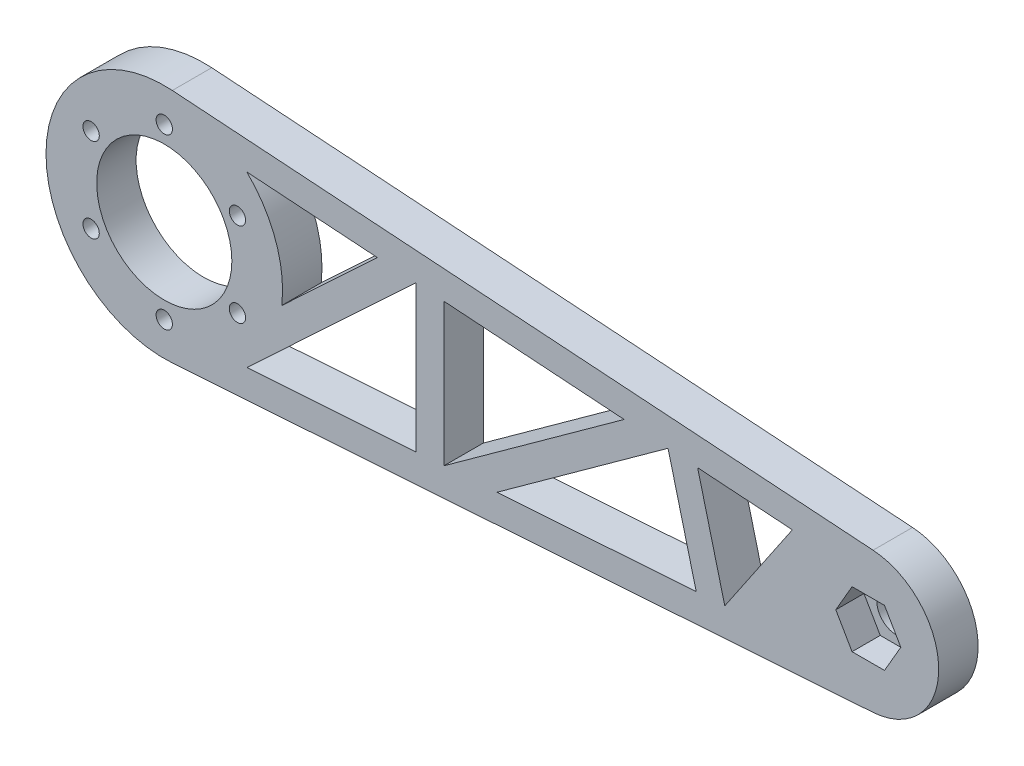
SolidWorks part; units mm, degrees
material "ABS"
ref_plane "前视基准面" through (0, 0, 0) normal (0, 0, 1) x (1, 0, 0)
ref_plane "上视基准面" through (0, 0, 0) normal (0, 1, 0) x (1, 0, 0)
ref_plane "右视基准面" through (0, 0, 0) normal (1, 0, 0) x (0, 0, -1)
other "Configuration Table"
sketch "草图2" plane through (0, 0, 0) normal (0, 0, 1) x (1, 0, 0)
  line L0 (0, 0) -> (125, 0) construction
  line L1 (1.428, 20.9514) -> (125.85, 12.4711)
  line L2 (1.428, -20.9514) -> (125.85, -12.4711)
  arc A0 (1.428, 20.9514) -> (1.428, -20.9514) centre (0, 0) ccw
  arc A1 (125.85, -12.4711) -> (125.85, 12.4711) centre (125, 0) ccw
  dimension "D2" = 21
  dimension "D3" = 25
  dimension "D1" = 125
extrude "凸台-拉伸1" add sketch "草图2" along normal blind 7
sketch "草图3" plane through (0, 0, 7) normal (0, 0, 1) x (1, 0, 0)
  line L0 (0, 0) -> (125, 0) construction
  line L1 (14.658, 15.0381) -> (115.5331, 8.1626) construction
  line L2 (125.85, 12.4711) -> (1.428, 20.9514) construction
  line L3 (14.658, -15.0381) -> (115.5331, -8.1626) construction
  line L4 (1.428, -20.9514) -> (125.85, -12.4711) construction
  line L5 (20.8627, -2.3975) -> (37.8323, 13.4586)
  line L6 (14.658, -15.0381) -> (44.658, 12.9933)
  line L7 (49.6464, -12.6533) -> (81.6464, 10.4723)
  line L10 (14.658, 15.0381) -> (37.8323, 13.4586)
  line L12 (49.6464, 12.6533) -> (44.658, 12.9933) construction
  line L13 (44.658, 12.9933) -> (44.658, -12.9933)
  line L14 (49.6464, 12.6533) -> (49.6464, -12.6533)
  line L15 (59.0717, -12.0109) -> (89.447, 9.9406)
  line L17 (14.658, -15.0381) -> (44.658, -12.9933)
  line L19 (49.6464, 12.6533) -> (81.6464, 10.4723)
  line L20 (89.447, 9.9406) -> (94.447, -9.5998)
  line L21 (94.6997, 9.5826) -> (99.5197, -9.2541)
  line L22 (99.5197, -9.2541) -> (111.5197, 8.4362)
  line L23 (111.5197, 8.4362) -> (94.6997, 9.5826)
  line L24 (94.447, -9.5998) -> (59.0717, -12.0109)
  line L25 (37.8323, 13.4586) -> (14.658, 15.0381)
  line L26 (37.8323, 13.4586) -> (14.658, 15.0381)
  circle A0 centre (0, 0) radius 21
  circle A1 centre (125, 0) radius 12.5
  point P13 (20.8627, -2.3975)
  dimension "D2" = 42
  dimension "D3" = 25
  dimension "D1" = 125
  dimension "D4" = 5
  dimension "D5" = 5
  dimension "D6" = 5
  dimension "D7" = 5
  dimension "D8" = 5
  dimension "D9" = 32
  dimension "D10" = 30
  dimension "D11" = 5
  dimension "D12" = 5
  dimension "D13" = 12
extrude "切除-拉伸1" cut sketch "草图3" against normal through all and the other way through all contours A0 L5 L10 | L12 L6 L3 | L19 L14 L7 | L24 L20 L15 | L22 L23 L21 region at (25.3755, 9.0284, 7) region at (34.658, -5.0127, 7) region at (60.3131, 3.4908, 7) region at (80.9886, -3.89, 7) region at (101.913, 2.9216, 7)
sketch "草图7" plane through (0, 0, 7) normal (0, 0, 1) x (1, 0, 0)
  line L0 (0, 0) -> (125, 0) construction
  line L1 (125, 0) -> (125, 5) construction
  line L2 (127.8797, 5) -> (122.1203, 5)
  line L3 (122.1203, 5) -> (125, 0) construction
  line L4 (127.8797, 5) -> (125, 0) construction
  line L5 (125, 0) -> (119.23, 0) construction
  line L6 (125, 0) -> (130.77, 0) construction
  line L7 (122.1203, 5) -> (119.23, 0)
  line L8 (127.8797, 5) -> (130.77, 0)
  line L9 (127.8797, -5) -> (130.77, 0)
  line L10 (127.8797, -5) -> (122.1203, -5)
  line L11 (122.1203, -5) -> (119.23, 0)
  dimension "D1" = 125
  dimension "D2" = 5
  dimension "D3" = 5.77
  dimension "D4" = 5.77
  dimension "D5" = 5.77
extrude "切除-拉伸2" cut sketch "草图7" against normal blind 5
sketch "草图11" plane through (0, 0, 0) normal (0, 0, -1) x (-1, 0, 0)
  point P0 (-125, 0)
ref_axis "基准轴1" through (125, 0, 0) along (0, 0, 1)
sketch "草图12" plane through (0, 0, 7) normal (0, 0, 1) x (1, 0, 0)
  circle A0 centre (0, 0) radius 15 construction
  circle A1 centre (0, 15) radius 1.45
  circle A7 centre (12.9904, 7.5) radius 1.45
  circle A8 centre (12.9904, -7.5) radius 1.45
  circle A9 centre (0, -15) radius 1.45
  circle A10 centre (-12.9904, -7.5) radius 1.45
  circle A11 centre (-12.9904, 7.5) radius 1.45
  point P18 (0, 0)
  dimension "D1" = 30
  dimension "D2" = 2.9
  dimension "D4" = 15
  dimension "D3" = 6
extrude "切除-拉伸3" cut sketch "草图12" against normal through all contours A1 | A7 | A8 | A9 | A10 | A11 region at (0, 15, 7) region at (12.9904, 7.5, 7) region at (12.9904, -7.5, 7) region at (0, -15, 7) region at (-12.9904, -7.5, 7)
sketch "草图14" plane through (0, 0, 7) normal (0, 0, 1) x (1, 0, 0)
  circle A0 centre (0, 0) radius 12
  dimension "D1" = 24
extrude "切除-拉伸4" cut sketch "草图14" against normal through all contours A0
sketch "草图15" plane through (0, 0, 0) normal (0, 0, -1) x (-1, 0, 0)
  circle A0 centre (-125, 0) radius 3.5
  dimension "D1" = 7
extrude "切除-拉伸5" cut sketch "草图15" against normal blind 10 contours A0 region at (125, 0, 0)
sketch "草图16" plane through (0, 0, 0) normal (0, 0, -1) x (-1, 0, 0)
  circle A0 centre (0, 15) radius 2.8
  dimension "D1" = 5.6
extrude "切除-拉伸6" cut sketch "草图16" against normal blind 3
pattern_circular "阵列(圆周)1" count 6 over 360 about axis through (0, 0, 0) along (0, 0, 1) of "切除-拉伸6"
